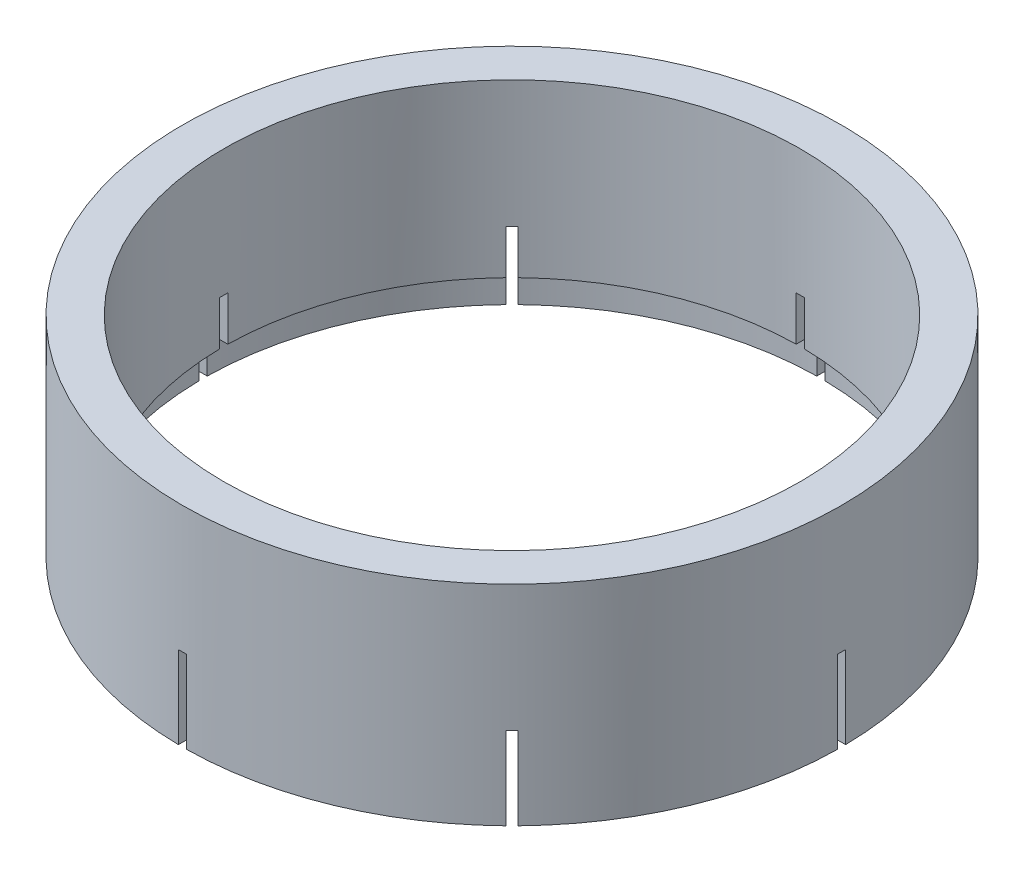
SolidWorks part; units mm, degrees
material "C (Graphite)"
ref_plane "Front Plane" through (0, 0, 0) normal (0, 0, 1) x (1, 0, 0)
ref_plane "Top Plane" through (0, 0, 0) normal (0, 1, 0) x (1, 0, 0)
ref_plane "Right Plane" through (0, 0, 0) normal (1, 0, 0) x (0, 0, -1)
sketch "Sketch1" plane through (0, 0, 0) normal (0, 1, 0) x (1, 0, 0)
  circle A0 centre (0, 0) radius 40
  circle A1 centre (0, 0) radius 35
  dimension "D1" = 80
  dimension "D2" = 70
extrude "Boss-Extrude1" add sketch "Sketch1" along normal blind 25.4
sketch "Sketch2" plane through (0, 0, 0) normal (0, -1, 0) x (1, 0, 0)
  circle A0 centre (0, 0) radius 37.5
  circle A1 centre (0, 0) radius 35
  dimension "D1" = 75
  dimension "D2" = 70
extrude "Cut-Extrude1" cut sketch "Sketch2" against normal blind 4.6
sketch "Sketch3" plane through (0, 0, 0) normal (0, 0, 1) x (1, 0, 0)
  line L0 (44, 0) -> (-44, 0) construction
  line L1 (-0.5, 0) -> (0.5, 0)
  line L2 (-0.5, 0) -> (-0.5, 10)
  line L3 (-0.5, 10) -> (0.5, 10)
  line L4 (0.5, 0) -> (0.5, 10)
  line L5 (0, -13.97) -> (0, 13.97) construction
  point P6 (0, 10)
  dimension "D1" = 0
  dimension "D2" = 1
  dimension "D3" = 10
extrude "Cut-Extrude2" cut sketch "Sketch3" against normal through all both and the other way through all
pattern_circular "CirPattern1" count 4 every 45 about axis through (0, 25.4, 0) along (0, -1, 0) of "Cut-Extrude2"
